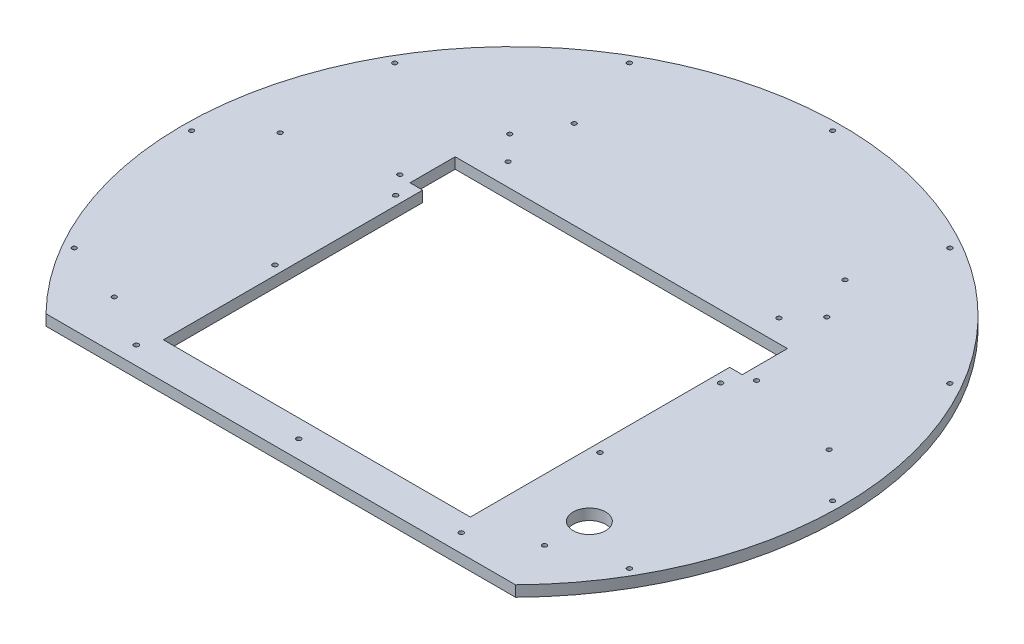
SolidWorks part; units mm, degrees
ref_plane "Front Plane" through (0, 0, 0) normal (0, 0, 1) x (1, 0, 0)
ref_plane "Top Plane" through (0, 0, 0) normal (0, 1, 0) x (1, 0, 0)
ref_plane "Right Plane" through (0, 0, 0) normal (1, 0, 0) x (0, 0, -1)
sketch "Sketch1" plane through (0, 0, 0) normal (0, 1, 0) x (1, 0, 0)
  line L0 (0, 0) -> (0, -162.5) construction
  line L2 (-100, -144.5) -> (100, -144.5)
  line L3 (-100, -144.5) -> (-100, 35.5)
  line L4 (-100, 35.5) -> (100, 35.5)
  line L5 (100, -144.5) -> (100, 35.5)
  line L6 (-100, -144.5) -> (100, 35.5) construction
  line L7 (-100, 35.5) -> (100, -144.5) construction
  circle A0 centre (0, 0) radius 162.5
  point P4 (0, -54.5)
  dimension "D1" = 325
  dimension "D2" = 180
  dimension "D3" = 35.5
  dimension "D4" = 200
sketch "Sketch2" plane through (0, 0, 0) normal (0, 1, 0) x (1, 0, 0)
  line L0 (-100, -144.5) -> (-100, 35.5) construction
  line L1 (-100, 35.5) -> (100, 35.5) construction
  line L2 (100, -144.5) -> (100, 35.5) construction
  line L3 (-100, -128.0869) -> (-100, 35.5)
  line L4 (-100, 35.5) -> (100, 35.5)
  line L5 (100, -128.0869) -> (100, 35.5)
  circle A0 centre (0, 0) radius 162.5 construction
  arc A1 (100, -128.0869) -> (-100, -128.0869) centre (0, 0) ccw
extrude "Boss-Extrude1" add sketch "Sketch2" along normal blind 6
sketch "Sketch4" plane through (0, 6, 0) normal (0, 1, 0) x (1, 0, 0)
  line L0 (0, 0) -> (0, 162.5) construction
  line L1 (119.15, -101.1581) -> (123.8764, -105.1708) construction
  line L2 (100, 35.5) -> (100, -128.0869) construction
  line L4 (-100, 35.5) -> (100, 35.5) construction
  arc A0 (100, -128.0869) -> (-100, -128.0869) centre (0, 0) ccw construction
  circle A1 centre (119.15, -101.1581) radius 1.25
  circle A2 centre (87.75, 86.5) radius 1.25
  circle A3 centre (152, 23.5891) radius 1.25
  circle A4 centre (-87.75, 86.5) radius 1.25
  circle A5 centre (98.75, 36.6) radius 1.25
  circle A6 centre (-98.75, 36.6) radius 1.25
  circle A7 centre (-152, 23.5891) radius 1.25
  circle A8 centre (-119.15, -101.1581) radius 1.25
  dimension "D1" = 2.5
  dimension "D3" = 6.2
  dimension "D2" = 129
  dimension "D4" = 19.15
  dimension "D5" = 52
  dimension "D6" = 51
  dimension "D7" = 87.75
  dimension "D8" = 1.1
extrude "Cut-Extrude2" cut sketch "Sketch4" against normal through all
sketch "Sketch5" plane through (0, 6, 0) normal (0, 1, 0) x (1, 0, 0)
  line L0 (-100, -128.0869) -> (-100, 35.5) construction
  line L1 (-100, -108.0869) -> (100, -108.0869)
  line L2 (-100, -108.0869) -> (-100, -128.0869)
  line L3 (-100, -128.0869) -> (100, -128.0869)
  line L4 (100, -108.0869) -> (100, -128.0869)
  dimension "D1" = 20
extrude "Boss-Extrude2" add sketch "Sketch5" against normal blind 6
sketch "Sketch6" plane through (0, 6, 0) normal (0, 1, 0) x (1, 0, 0)
  line L0 (0, 0) -> (0, 162.5) construction
  line L1 (-100, 35.5) -> (-99.3437, 35.5) construction
  line L2 (-92, 60.5) -> (92, 60.5)
  line L3 (-92, 60.5) -> (-92, 35.5)
  line L4 (-92, 35.5) -> (92, 35.5)
  line L5 (92, 60.5) -> (92, 35.5)
  line L6 (-92, 60.5) -> (92, 35.5) construction
  line L7 (-92, 35.5) -> (92, 60.5) construction
  line L8 (100, 35.5) -> (100, -108.0869) construction
  arc A0 (100, -128.0869) -> (-100, -128.0869) centre (0, 0) ccw construction
  point P6 (0, 48)
  dimension "D1" = 8
  dimension "D2" = 25
extrude "Cut-Extrude3" cut sketch "Sketch6" against normal through all
sketch "Sketch7" plane through (0, 6, 0) normal (0, 1, 0) x (1, 0, 0)
  line L0 (0, 0) -> (0, 162.5) construction
  line L1 (92, 60.5) -> (-92, 60.5) construction
  circle A0 centre (-75, 72.8) radius 1.25
  circle A1 centre (-75, 109.4) radius 1.25
  arc A2 (100, -128.0869) -> (-100, -128.0869) centre (0, 0) ccw construction
  circle A3 centre (75, 109.4) radius 1.25
  circle A4 centre (75, 72.8) radius 1.25
  dimension "D4" = 2.5
  dimension "D1" = 36.6
  dimension "D2" = 150
  dimension "D3" = 12.3
extrude "Cut-Extrude4" cut sketch "Sketch7" against normal blind 6
sketch "Sketch8" plane through (0, 6, 0) normal (0, 1, 0) x (1, 0, 0)
  line L0 (-100, -128.0869) -> (-130, -128.0869)
  line L1 (100, -128.0869) -> (130, -128.0869)
  arc A0 (130, -128.0869) -> (-130, -128.0869) centre (0, 0) ccw
  arc A1 (100, -128.0869) -> (-100, -128.0869) centre (0, 0) ccw construction
  arc A2 (100, -128.0869) -> (-100, -128.0869) centre (0, 0) ccw
  dimension "D1" = 20
extrude "Boss-Extrude3" add sketch "Sketch8" against normal through all
sketch "Sketch9" plane through (0, 6, 0) normal (0, 1, 0) x (1, 0, 0)
  line L0 (0, 182.5) -> (0, 162.5) construction
  arc A0 (130, -128.0869) -> (-130, -128.0869) centre (0, 0) ccw construction
  circle A1 centre (0, 0) radius 162.5 construction
  circle A2 centre (0, 177.5) radius 1.25
  circle A3 centre (88.75, 153.7195) radius 1.25
  circle A4 centre (153.7195, 88.75) radius 1.25
  circle A5 centre (177.5, 0) radius 1.25
  circle A6 centre (153.7195, -88.75) radius 1.25
  circle A7 centre (88.75, -153.7195) radius 1.25
  circle A8 centre (0, -177.5) radius 1.25
  circle A9 centre (-88.75, -153.7195) radius 1.25
  circle A10 centre (-153.7195, -88.75) radius 1.25
  circle A11 centre (-177.5, 0) radius 1.25
  circle A12 centre (-153.7195, 88.75) radius 1.25
  circle A13 centre (-88.75, 153.7195) radius 1.25
  point P36 (0, 0)
  dimension "D1" = 2.5
  dimension "D3" = 5
  dimension "D2" = 12
extrude "Cut-Extrude5" cut sketch "Sketch9" against normal through all
sketch "Sketch10" plane through (0, 6, 0) normal (0, 1, 0) x (1, 0, 0)
  line L0 (-100, 35.5) -> (100, 35.5) construction
  line L1 (-100, -108.0869) -> (-85, -108.0869)
  line L2 (-100, -108.0869) -> (-100, 35.5)
  line L3 (-100, 35.5) -> (-85, 35.5)
  line L4 (-85, -108.0869) -> (-85, 35.5)
  line L5 (0, 0) -> (0, 60.5) construction
  line L6 (92, 60.5) -> (-92, 60.5) construction
  line L7 (85, -108.0869) -> (85, 35.5)
  line L8 (100, 35.5) -> (85, 35.5)
  line L9 (100, -108.0869) -> (100, 35.5)
  line L10 (100, -108.0869) -> (85, -108.0869)
  dimension "D1" = 15
extrude "Boss-Extrude4" add sketch "Sketch10" against normal through all
sketch "Sketch11" plane through (0, 6, 0) normal (0, 1, 0) x (1, 0, 0)
  line L0 (-139.1465, -118.0869) -> (139.1465, -118.0869) construction
  line L1 (-130, -128.0869) -> (130, -128.0869) construction
  line L2 (-90, -118.0869) -> (-90, 35.5) construction
  line L3 (-100, 35.5) -> (100, 35.5) construction
  line L4 (-100, -144.5) -> (-100, 35.5) construction
  line L5 (90, 35.5) -> (90, -118.0869) construction
  line L6 (100, -144.5) -> (100, 35.5) construction
  line L7 (0, 0) -> (0, 60.5) construction
  line L8 (92, 60.5) -> (-92, 60.5) construction
  arc A0 (130, -128.0869) -> (-130, -128.0869) centre (0, 0) ccw construction
  circle A1 centre (-90, -118.0869) radius 1.3
  circle A2 centre (0, -118.0869) radius 1.3
  circle A3 centre (90, -118.0869) radius 1.3
  circle A4 centre (-90, 25.5) radius 1.3
  circle A5 centre (-90, -41.2934) radius 1.3
  circle A6 centre (90, -41.2934) radius 1.3
  circle A7 centre (90, 25.5) radius 1.3
  dimension "D5" = 2.6
  dimension "D1" = 10
  dimension "D2" = 10
  dimension "D3" = 10
  dimension "D4" = 10
extrude "Cut-Extrude6" cut sketch "Sketch11" against normal through all
sketch "Sketch12" plane through (0, 6, 0) normal (0, 1, 0) x (1, 0, 0)
  line L0 (119.15, -101.1581) -> (120, -77.1732) construction
  circle A0 centre (120, -77.1732) radius 9
  dimension "D2" = 18
  dimension "D1" = 24
  dimension "D3" = 28
extrude "Cut-Extrude7" cut sketch "Sketch12" against normal through all
